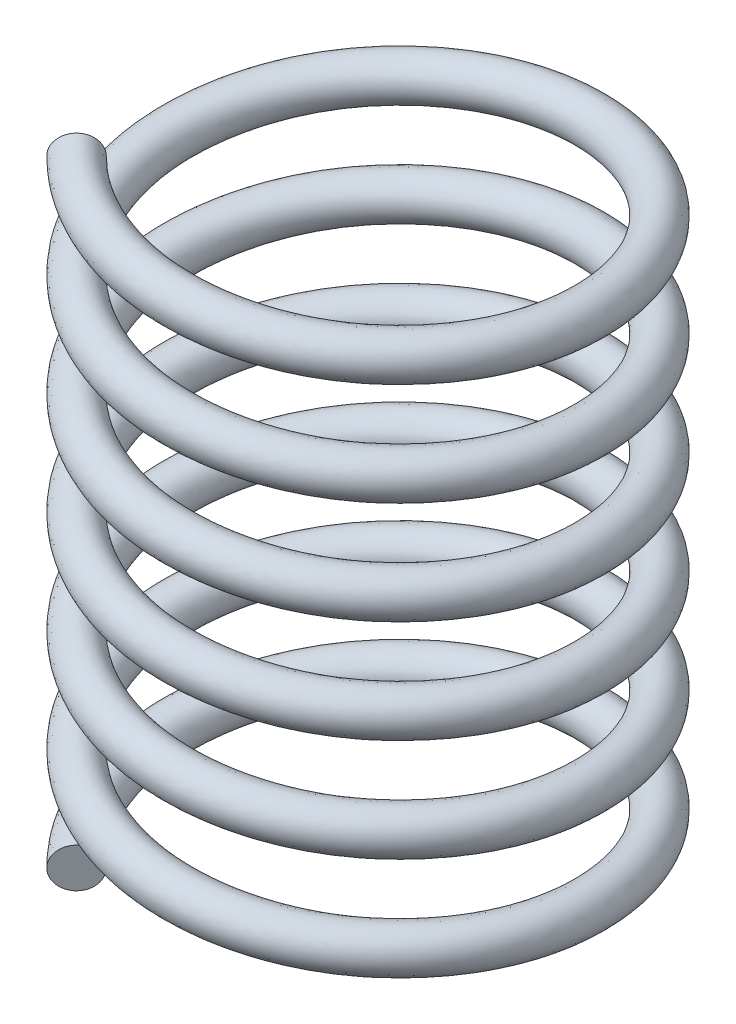
SolidWorks part; units mm, degrees
note: The reader was unsure of these and kept them because the rebuilt part matched: shared geometry of "Sketch1<2>".
ref_plane "Front Plane" through (0, 0, 0) normal (0, 0, 1) x (1, 0, 0)
ref_plane "Top Plane" through (0, 0, 0) normal (0, 1, 0) x (1, 0, 0)
ref_plane "Right Plane" through (0, 0, 0) normal (1, 0, 0) x (0, 0, -1)
sketch "Sketch1" plane through (0, 0, 0) normal (0, 1, 0) x (1, 0, 0)
  circle A0 centre (0, 0) radius 3.175
  dimension "D1" = 6.35
curve "Helix/Spiral1" pitch 1.5875 height 9.525 turns 6 parameters "length"=9.525
ref_plane "Plane2" through (-2.2451, 0, 2.2451) normal (-0.7049, 0.0793, -0.7049) x (-0.6978, 0.1008, 0.7092)
sketch "Sketch4" plane through (-2.2451, 0, 2.2451) normal (-0.7049, 0.0793, -0.7049) x (-0.6978, 0.1008, 0.7092)
  circle A0 centre (0.0093, 0.0036) radius 0.325
  dimension "D1" = 0.65
sweep "Sweep1" add profiles "Sketch4" path "Helix/Spiral1"
surface "Surface-Extrude2" sketch "Sketch1<2>"
sketch "Sketch1<2>" plane through (0, 0, 0) normal (0, 1, 0) x (1, 0, 0) same geometry as "Sketch1"
